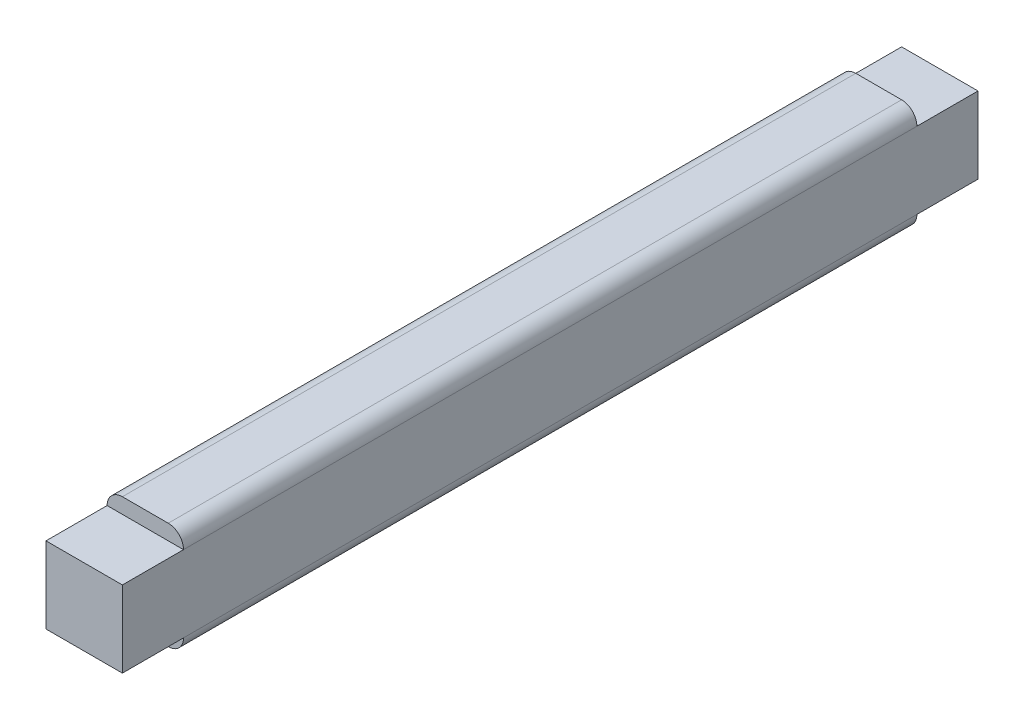
SolidWorks part; units mm, degrees
ref_plane "Plan de face" through (0, 0, 0) normal (0, 0, 1) x (1, 0, 0)
ref_plane "Plan de dessus" through (0, 0, 0) normal (0, 1, 0) x (1, 0, 0)
ref_plane "Plan de droite" through (0, 0, 0) normal (1, 0, 0) x (0, 0, -1)
sketch "Esquisse1" plane through (0, 0, 0) normal (0, 0, 1) x (1, 0, 0)
  line L1 (0, 0) -> (25, 0)
  line L2 (0, 0) -> (0, 35)
  line L3 (0, 35) -> (25, 35)
  line L4 (25, 0) -> (25, 35)
  dimension "D1" = 25
  dimension "D2" = 35
extrude "Boss.-Extru.1" add sketch "Esquisse1" along normal blind 280
sketch "Esquisse2" plane through (0, 0, 280) normal (0, 0, 1) x (1, 0, 0)
  line L0 (0, 17.5) -> (25, 17.5) construction
  line L1 (0, 35) -> (0, 0) construction
  line L2 (25, 0) -> (25, 35) construction
  line L3 (0, 5) -> (0, 30)
  line L4 (12.5, 5) -> (12.5, 30) construction
  line L5 (25, 30) -> (0, 30)
  line L6 (25, 5) -> (0, 5)
  line L7 (25, 5) -> (25, 30)
  point P11 (12.5, 17.5)
  point P12 (0, 17.5)
  point P14 (25, 17.5)
  dimension "D1" = 25
  dimension "D2" = 25
extrude "Enlèv. mat.-Extru.2" cut sketch "Esquisse2" against normal blind 20 flip side to cut
extrude "Enlèv. mat.-Extru.3" cut sketch "Esquisse2<2>" along normal blind 20 from surface flip side to cut starting at face at (12.5, 17.5, 0)
sketch "Esquisse2<2>" plane through (0, 0, 280) normal (0, 0, 1) x (1, 0, 0) same geometry as "Esquisse2"
fillet "Congé1" radius 5 4 edges at (0, 0, 140) (25, 0, 140) (25, 35, 140) (0, 35, 140)
